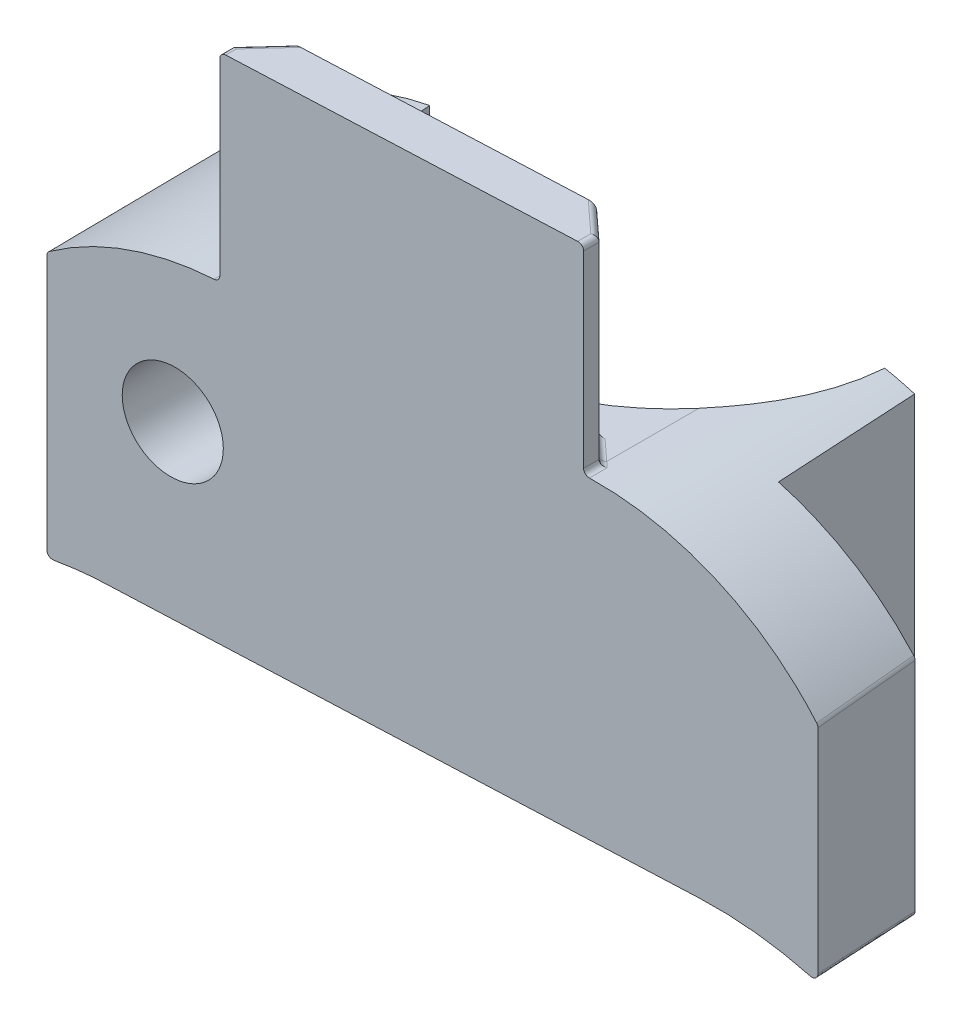
SolidWorks part; units mm, degrees
material "ABS"
ref_plane "Plan de face" through (0, 0, 0) normal (0, 0, 1) x (1, 0, 0)
ref_plane "Plan de dessus" through (0, 0, 0) normal (0, 1, 0) x (1, 0, 0)
ref_plane "Plan de droite" through (0, 0, 0) normal (1, 0, 0) x (0, 0, -1)
sketch "Esquisse16" plane through (0, 0, 0) normal (0, 0, 1) x (1, 0, 0)
  line L3 (-12.3653, -0.2302) -> (-12.3653, 8.8081)
  line L4 (-10, 0) -> (7.7, 0)
  line L5 (7.7, 10.874) -> (7.7, 0)
  line L6 (-6.1176, 11) -> (6.1176, 11)
  line L7 (0, 0) -> (0, 11) construction
  arc A3 (-6.1176, 11) -> (-12.3653, 8.8081) centre (-6.1176, 1) ccw
  arc A4 (-10, 0) -> (-12.3653, -0.2302) centre (-10, -12.2656) ccw
  arc A5 (7.7, 10.874) -> (6.1176, 11) centre (6.1176, 1) ccw
  circle A6 centre (-7.7, 6) radius 1.7
  dimension "D4" = 12.2656
  dimension "D7" = 10
  dimension "D9" = 10
  dimension "D11" = 3.4
  dimension "D1" = 7.7
  dimension "D2" = 5
  dimension "D3" = 20.0653
  dimension "D5" = 17.7
  dimension "D6" = 7.7
  dimension "D8" = 11
  dimension "D10" = 9.0383
  dimension "D12" = 12.2352
extrude "Boss.-Extru.5" add sketch "Esquisse16" against normal blind 10
sketch "Esquisse27" plane through (0, 0, -10) normal (0, 0, -1) x (-1, 0, 0)
  line L0 (10, 0) -> (-7.7, 0) construction
  line L3 (-7.7, 10.874) -> (-7.7, 0)
  line L4 (3.3676, -3.9913) -> (3.3676, 15.0996) construction
  line L5 (-7.7, 0) -> (-10, 0)
  line L6 (-14, -0.6706) -> (-14, 7.1537)
  arc A0 (-6.1176, 11) -> (-7.7, 10.874) centre (-6.1176, 1) ccw construction
  arc A1 (12.3653, 8.8081) -> (6.1176, 11) centre (6.1176, 1) ccw construction
  arc A2 (12.3653, -0.2302) -> (10, 0) centre (10, -12.2656) ccw construction
  arc A5 (-14, -0.6706) -> (-10, 0) centre (-10, -12.2656) cw
  arc A6 (-14, 7.1537) -> (-7.7, 10.874) centre (-6.1176, 1) cw
  dimension "D1" = 6.3
  dimension "D2" = 2.3
extrude "Boss.-Extru.8" add sketch "Esquisse27" against normal blind 10 contours A6 L3 L5 A5 L6
sketch "Esquisse21" plane through (0, 11, 0) normal (0, 1, 0) x (1, 0, 0)
  line L0 (14, 0) -> (14, 1.1412)
  line L1 (-12.3653, 10) -> (-11.9333, 0.0187)
  line L2 (14, 1.1412) -> (-11.9333, 0.0187)
  line L3 (-12.3653, 0) -> (14, 0)
  line L4 (14, 0) -> (14, 10) construction
  line L5 (6.1176, 0.8) -> (6.1176, 0) construction
  line L6 (6.1176, 10) -> (6.1176, 0) construction
  line L7 (-12.3653, 0) -> (-12.3653, 10)
  dimension "D1" = 0.8
  dimension "D2" = 87.522
extrude "Enlèv. mat.-Extru.8" cut sketch "Esquisse21" against normal blind 13
sketch "Esquisse17" plane through (0, 11, 0) normal (0, 1, 0) x (1, 0, 0)
  line L0 (6.1176, 0.8) -> (-6.1176, 0.2704) construction
  line L6 (6.1176, 1.3411) -> (6.1176, 0.8)
  line L7 (6.1176, 0.8) -> (-6.1176, 0.2704)
  line L8 (5.1176, 2.2581) -> (6.1176, 1.3411)
  line L9 (5.1176, 2.2581) -> (-5.1176, 1.8151)
  line L10 (-5.1176, 1.8151) -> (-6.1176, 0.7246)
  line L11 (-6.1176, 0.7246) -> (-6.1176, 0.2704)
  line L13 (-6.1176, 10) -> (-6.1176, 0.2704) construction
  line L14 (6.1176, 10) -> (6.1176, 0.8) construction
  dimension "D1" = 1.5
  dimension "D2" = 135
  dimension "D3" = 135
  dimension "D4" = 1
  dimension "D5" = 1
extrude "Boss.-Extru.6" add sketch "Esquisse17" along normal blind 7
sketch "Esquisse18" plane through (0, 0, -10) normal (0, 0, -1) x (-1, 0, 0)
  line L0 (8, 11) -> (8, 8.2)
  line L2 (8, 8.2) -> (6, 8.2)
  line L3 (6, 8.2) -> (6, 4)
  line L4 (6, 4) -> (8, 4)
  line L5 (8, 4) -> (8, 0)
  line L7 (8, 0) -> (0, 0)
  line L8 (0, 0) -> (0, 11)
  line L9 (0, 11) -> (8, 11)
  line L10 (0, 11) -> (0, 4.0607) construction
  line L13 (10, 0) -> (-10, 0) construction
  line L14 (-6.1176, 11) -> (6.1176, 11) construction
  dimension "D1" = 6
  dimension "D2" = 8
  dimension "D3" = 8
  dimension "D4" = 4.2
  dimension "D5" = 2.8
revolve "Enlèvement de matière-Révolution2" cut sketch "Esquisse18" angle 360 about L10
sketch "Esquisse15" plane through (0, 8.2, 0) normal (0, 1, 0) x (1, 0, 0)
  line L0 (-4.8734, 6.5) -> (-7.1937, 6.5)
  line L1 (-6, 10) -> (-8, 10)
  line L6 (-6, 10) -> (-8, 10) construction
  arc A1 (-7.1937, 6.5) -> (-8, 10) centre (0, 10) cw
  arc A4 (-4.8734, 6.5) -> (-6, 10) centre (0, 10) cw
  arc A7 (-6, 10) -> (6, 10) centre (0, 10) ccw construction
  arc A8 (-8, 10) -> (8, 10) centre (0, 10) ccw construction
  dimension "D1" = 3.5
extrude "Enlèv. mat.-Extru.6" cut sketch "Esquisse15" against normal blind 5
sketch "Esquisse19" plane through (0, 11, 0) normal (0, 1, 0) x (1, 0, 0)
  line L1 (14, 10) -> (-12.3653, 10)
  line L2 (14, 10) -> (14, 9.5)
  line L3 (14, 9.5) -> (-12.3653, 9.5)
  line L4 (-12.3653, 10) -> (-12.3653, 9.5)
  dimension "D1" = 0.5
extrude "Enlèv. mat.-Extru.7" cut sketch "Esquisse19" against normal blind 15
sketch "Esquisse28" plane through (0, 18, 0) normal (0, 1, 0) x (1, 0, 0)
  line L0 (14, 9.5) -> (7.9844, 9.5) construction
  line L1 (9.0339, 9.5) -> (14, 9.5)
  line L2 (9.0339, 9.5) -> (9.2501, 4.5047)
  line L3 (9.2501, 4.5047) -> (13.8458, 4.7036)
  line L4 (13.8458, 4.7036) -> (14, 1.1412)
  line L6 (6.1176, 0.8) -> (14, 1.1412) construction
  line L8 (14, 1.1412) -> (14, 9.5)
  dimension "D1" = 5
  dimension "D2" = 4.6
extrude "Enlèv. mat.-Extru.9" cut sketch "Esquisse28" against normal blind 21
fillet "Congé1" radius 0.2 12 edges at (-12.1405, 8.9828, -4.8053) (-5.6176, 11, -1.2699) (5.6176, 11, -1.7996) (5.6176, 18, -1.7996) (-5.6176, 18, -1.2699) (6.1176, 11, -1.0705) (6.1176, 18, -1.0705) (-6.1176, 18, -0.4975) (-6.1176, 11, -0.4975) (-12.1388, -0.1879, -4.7665) (13.9235, 7.2505, -2.9087) (13.923, -0.6443, -2.9204)
